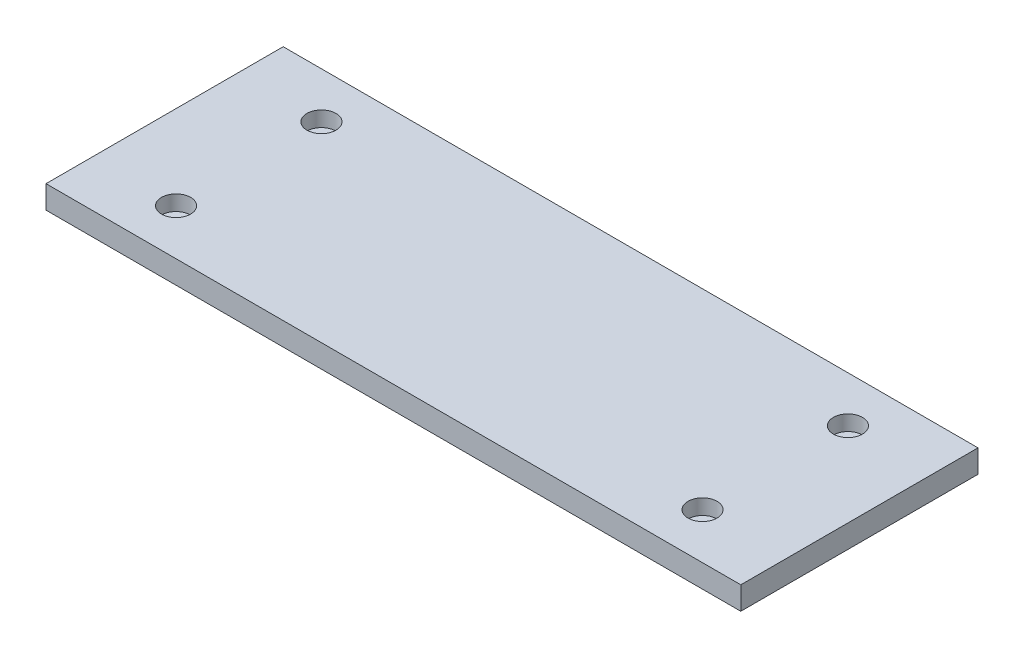
SolidWorks part; units mm, degrees
ref_plane "Front Plane" through (0, 0, 0) normal (0, 0, 1) x (1, 0, 0)
ref_plane "Top Plane" through (0, 0, 0) normal (0, 1, 0) x (1, 0, 0)
ref_plane "Right Plane" through (0, 0, 0) normal (1, 0, 0) x (0, 0, -1)
sketch "Sketch1" plane through (0, 0, 0) normal (0, 1, 0) x (1, 0, 0)
  line L0 (-45.4, 0) -> (45.4, 0) construction
  line L1 (-45.4, 15.5) -> (45.4, 15.5)
  line L2 (-45.4, 15.5) -> (-45.4, -15.5)
  line L3 (-45.4, -15.5) -> (45.4, -15.5)
  line L4 (45.4, 15.5) -> (45.4, -15.5)
  line L5 (0, 15.5) -> (0, -15.5) construction
  point P8 (0, 0)
  dimension "D1" = 90.8
  dimension "D2" = 31
extrude "Boss-Extrude1" add sketch "Sketch1" along normal blind 3
sketch "Sketch2" plane through (0, 3, 0) normal (0, 1, 0) x (1, 0, 0)
  line L0 (-34.4, 9.5) -> (-45.4, 9.5) construction
  line L1 (-45.4, 15.5) -> (-45.4, -15.5) construction
  line L2 (-34.4, -9.5) -> (-45.4, -9.5) construction
  line L3 (34.4, 9.5) -> (45.4, 9.5) construction
  line L4 (45.4, -15.5) -> (45.4, 15.5) construction
  line L5 (34.4, -9.5) -> (45.4, -9.5) construction
  line L6 (-34.4, 9.5) -> (-34.4, 15.5) construction
  line L7 (45.4, 15.5) -> (-45.4, 15.5) construction
  line L8 (34.4, 9.5) -> (34.4, 15.5) construction
  line L9 (34.4, -9.5) -> (34.4, -15.5) construction
  line L10 (-45.4, -15.5) -> (45.4, -15.5) construction
  line L11 (-34.4, -9.5) -> (-34.4, -15.5) construction
  circle A0 centre (-34.4, 9.5) radius 0.95
  circle A1 centre (34.4, 9.5) radius 0.95
  circle A2 centre (-34.4, -9.5) radius 0.95
  circle A3 centre (34.4, -9.5) radius 0.95
  dimension "D1" = 1.9
  dimension "D2" = 6
  dimension "D3" = 11
extrude "Cut-Extrude1" cut sketch "Sketch2" against normal blind 3
sketch "Sketch3" plane through (0, 3, 0) normal (0, 1, 0) x (1, 0, 0)
  circle A0 centre (-34.4, 9.5) radius 1.9
  circle A1 centre (-34.4, -9.5) radius 1.9
  circle A2 centre (34.4, 9.5) radius 1.9
  circle A3 centre (34.4, -9.5) radius 1.9
  dimension "D1" = 3.8
extrude "Cut-Extrude2" cut sketch "Sketch3" against normal blind 2
sketch "Sketch4" plane through (0, 0, 0) normal (0, -1, 0) x (1, 0, 0)
  line L0 (-27, 0) -> (27, 0) construction
  line L1 (-27, 3.5) -> (27, 3.5)
  line L2 (-27, 3.5) -> (-27, -3.5)
  line L3 (-27, -3.5) -> (27, -3.5)
  line L4 (27, 3.5) -> (27, -3.5)
  line L5 (0, 3.5) -> (0, -3.5) construction
  point P8 (0, 0)
  dimension "D1" = 54
  dimension "D2" = 7
extrude "Boss-Extrude2" add sketch "Sketch4" along normal blind 6
sketch "Sketch5" plane through (27, 0, 0) normal (1, 0, 0) x (0, 0, -1)
  line L0 (0, -6) -> (0, -7.1307) construction
  line L1 (3.5, -6) -> (-3.5, -6) construction
  circle A0 centre (0, -7.1307) radius 3.9
  dimension "D1" = 7.8
  dimension "D2" = 1.1307
extrude "Cut-Extrude3" cut sketch "Sketch5" against normal blind 54
